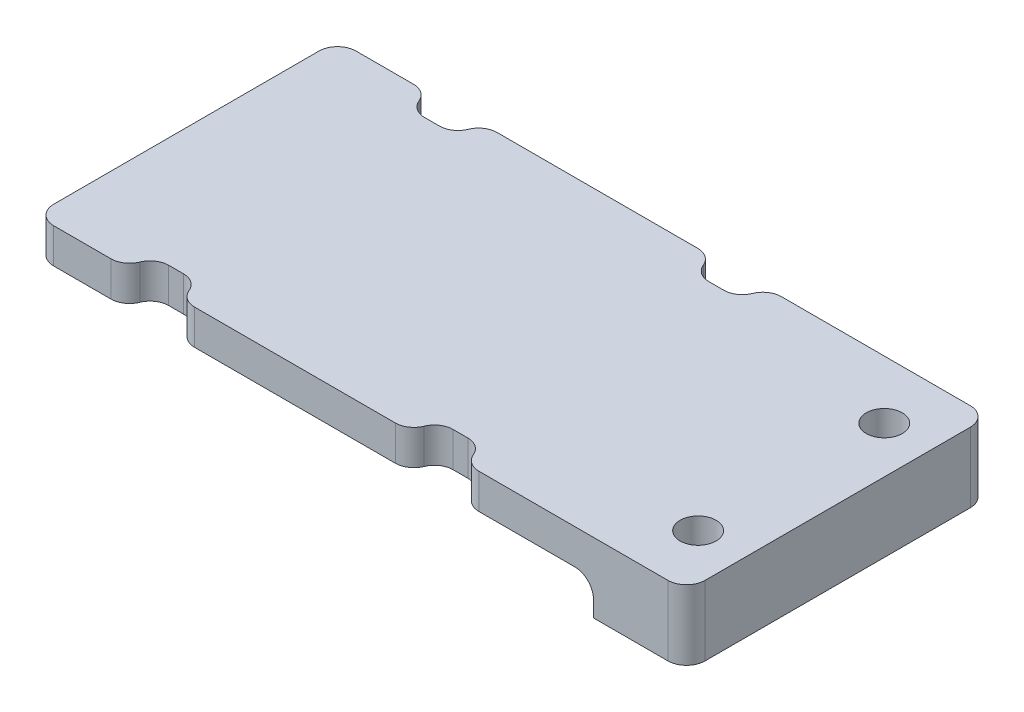
SolidWorks part; units mm, degrees
ref_plane "Front" through (0, 0, 0) normal (0, 0, 1) x (1, 0, 0)
ref_plane "Top" through (0, 0, 0) normal (0, 1, 0) x (1, 0, 0)
ref_plane "Right" through (0, 0, 0) normal (1, 0, 0) x (0, 0, -1)
sketch "Sketch1" plane through (0, 0, 0) normal (0, 1, 0) x (1, 0, 0)
  line L1 (-44.45, -20.6375) -> (44.45, -20.6375)
  line L2 (-44.45, -20.6375) -> (-44.45, 20.6375)
  line L3 (-44.45, 20.6375) -> (44.45, 20.6375)
  line L4 (44.45, -20.6375) -> (44.45, 20.6375)
  line L5 (-44.45, -20.6375) -> (44.45, 20.6375) construction
  line L6 (-44.45, 20.6375) -> (44.45, -20.6375) construction
  point P0 (0, 0)
  dimension "D1" = 88.9
  dimension "D2" = 41.275
extrude "Boss-Extrude1" add sketch "Sketch1" along normal blind 4.7625
sketch "Sketch3" plane through (0, 0, 0) normal (0, -1, 0) x (1, 0, 0)
  line L0 (44.45, -20.6375) -> (-44.45, -20.6375) construction
  line L1 (44.45, 20.6375) -> (31.75, 20.6375)
  line L2 (44.45, 20.6375) -> (44.45, -20.6375)
  line L3 (44.45, -20.6375) -> (31.75, -20.6375)
  line L4 (31.75, 20.6375) -> (31.75, -20.6375)
  dimension "D1" = 12.7
extrude "Boss-Extrude2" add sketch "Sketch3" along normal blind 4.7625
sketch "Sketch8" plane through (0, 4.7625, 0) normal (0, 1, 0) x (1, 0, 0)
  line L4 (44.45, -20.6375) -> (44.45, 20.6375) construction
  line L5 (-50, 0) -> (50, 0) construction
  point P0 (38.1, 12.7)
  point P4 (38.1, -12.7)
  point P29 (44.45, 11.93)
  dimension "D1" = 25.4
  dimension "D2" = 12.7
  dimension "D3" = 6.35
hole_wizard "#10 (0.1935) Diameter Hole1" positions "Sketch8" profile "Sketch7" hole size "#10" standard "ANSI Inch" end condition through all
sketch "Sketch7" plane through (38.1, 4.7625, -12.7) normal (1, 0, 0) x (0, 0, 1)
  line L0 (0, 0) -> (0, 9.525)
  line L1 (0, 9.525) -> (2.4574, 9.525)
  line L2 (2.4574, 9.525) -> (2.4574, 0)
  line L5 (2.4574, 0) -> (0, 0)
  line L11 (0, -6.35) -> (0, 107.95) construction
  dimension "Thru Hole Dia." = 4.9149
  dimension "Thru Hole Depth" = 9.525
sketch "Sketch9" plane through (0, 4.7625, 0) normal (0, 1, 0) x (1, 0, 0)
  line L14 (44.45, 20.6375) -> (-44.45, 20.6375) construction
  line L20 (7.248, 20.6375) -> (13.598, 20.6375)
  line L21 (7.248, 20.6375) -> (7.248, 17.4625)
  line L22 (7.248, 17.4625) -> (13.598, 17.4625)
  line L23 (13.598, 20.6375) -> (13.598, 17.4625)
  line L24 (-44.45, -20.6375) -> (44.45, -20.6375) construction
  line L25 (-31.5516, 20.6375) -> (-25.2016, 20.6375)
  line L26 (-31.5516, 20.6375) -> (-31.5516, 17.4625)
  line L27 (-31.5516, 17.4625) -> (-25.2016, 17.4625)
  line L28 (-25.2016, 20.6375) -> (-25.2016, 17.4625)
  line L29 (-31.5516, -20.6375) -> (-25.2016, -20.6375)
  line L30 (-31.5516, -20.6375) -> (-31.5516, -17.4625)
  line L31 (-31.5516, -17.4625) -> (-25.2016, -17.4625)
  line L32 (-25.2016, -20.6375) -> (-25.2016, -17.4625)
  line L34 (7.248, -20.6375) -> (13.598, -20.6375)
  line L35 (7.248, -20.6375) -> (7.248, -17.4625)
  line L36 (7.248, -17.4625) -> (13.598, -17.4625)
  line L37 (13.598, -20.6375) -> (13.598, -17.4625)
  line L38 (44.45, -20.6375) -> (44.45, 20.6375) construction
  dimension "D1" = 3.175
  dimension "D2" = 6.35
  dimension "D3" = 32.4495
  dimension "D4" = 76.0016
extrude "Cut-Extrude1" cut sketch "Sketch9" against normal through all
fillet "Fillet1" radius 2.54 12 edges at (-25.2016, 2.3812, 20.6375) (-31.5516, 2.3812, 20.6375) (-44.45, 2.3813, 20.6375) (-31.5516, 2.3812, -20.6375) (-25.2016, 2.3812, -20.6375) (7.248, 2.3812, -20.6375) (13.598, 2.3812, -20.6375) (44.45, 0, -20.6375) (44.45, 0, 20.6375) (13.598, 2.3812, 20.6375) (7.248, 2.3812, 20.6375) (-44.45, 2.3813, -20.6375)
fillet "Fillet2" radius 2.54 9 edges at (-31.5516, 2.3812, -17.4625) (-25.2016, 2.3813, -17.4625) (13.598, 2.3813, -17.4625) (7.248, 2.3812, -17.4625) (31.75, 0, 0) (13.598, 2.3813, 17.4625) (7.248, 2.3812, 17.4625) (-31.5516, 2.3812, 17.4625) (-25.2016, 2.3813, 17.4625)
